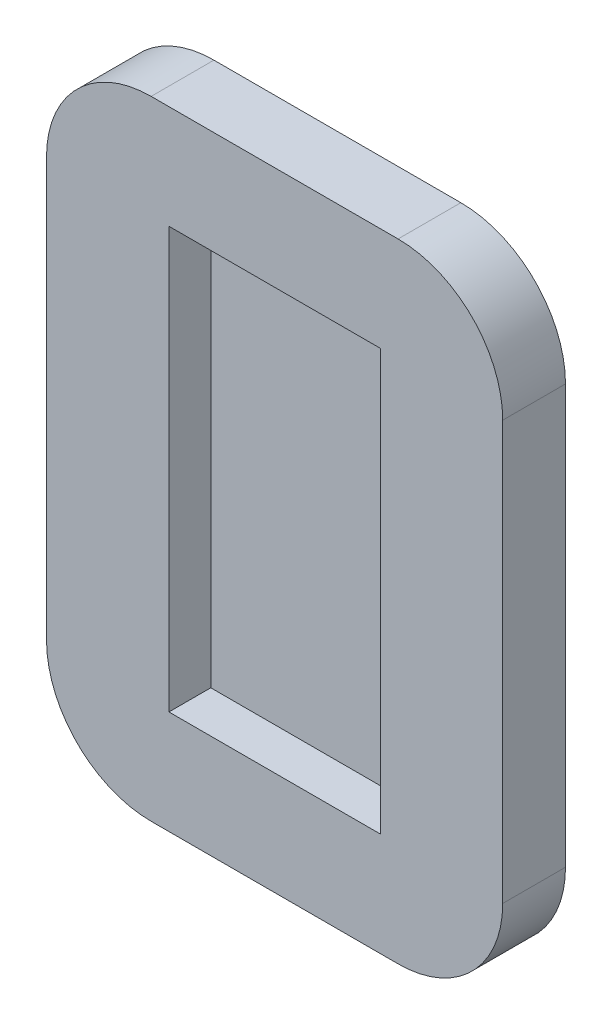
SolidWorks part; units mm, degrees
ref_plane "Alzado" through (0, 0, 0) normal (0, 0, 1) x (1, 0, 0)
ref_plane "Planta" through (0, 0, 0) normal (0, 1, 0) x (1, 0, 0)
ref_plane "Vista lateral" through (0, 0, 0) normal (1, 0, 0) x (0, 0, -1)
sketch "Croquis1" plane through (0, 0, 0) normal (1, 0, 0) x (0, 0, -1)
  line L1 (0, 0) -> (-21.8, 0)
  line L2 (0, 0) -> (0, -30)
  line L3 (0, -30) -> (-21.8, -30)
  line L4 (-21.8, 0) -> (-21.8, -30)
  dimension "D1" = 21.8
  dimension "D2" = 30
extrude "Saliente-Extruir1" add sketch "Croquis1" along normal blind 21.8 contours L2 L3 L4 L1
sketch "Croquis6" plane through (0, 0, 0) normal (-1, 0, 0) x (0, 0, 1)
  line L1 (10.9, -7) -> (10.9, 0) construction
  line L2 (10.9, -22) -> (10.9, -7) construction
  line L3 (0, 0) -> (21.8, 0) construction
  circle A0 centre (10.9, -22) radius 2
  circle A1 centre (10.9, -7) radius 2
  dimension "D1" = 15
  dimension "D3" = 4
  dimension "D4" = 4
  dimension "D2" = 7
extrude "Cortar-Extruir2" cut sketch "Croquis6" against normal up to surface (21.8 mm away) up to face at (21.8, -15, 10.9)
sketch "Croquis7" plane through (21.8, 0, 0) normal (1, 0, 0) x (0, 0, -1)
  line L2 (-10.9, -22) -> (-10.9, -7) construction
  circle A0 centre (-10.9, -22) radius 3.5
  circle A1 centre (-10.9, -7) radius 3.5
  circle A2 centre (-10.9, -7) radius 2 construction
  dimension "D1" = 7
  dimension "D2" = 7
  dimension "D3" = 15
sketch "Croquis11" plane through (0, -30, 0) normal (0, -1, 0) x (1, 0, 0)
  line L0 (13.4, 5.9) -> (13.4, 10.9) construction
  line L1 (0, 0) -> (0, 21.8) construction
  line L2 (0, 0) -> (0, 21.8) construction
  line L7 (16.9, 10.9) -> (21.8, 10.9) construction
  line L8 (13.4, 10.9) -> (8.9, 10.9) construction
  line L9 (8.9, 15.1) -> (5.5, 15.1)
  line L14 (8.9, 15.1) -> (8.9, 6.7)
  line L16 (8.9, 6.7) -> (5.5, 6.7)
  line L17 (5.5, 15.1) -> (5.5, 6.7)
  line L18 (21.8, 0) -> (21.8, 21.8) construction
  line L19 (5.5, 10.9) -> (0, 10.9) construction
  circle A1 centre (13.4, 10.9) radius 3.5
  dimension "D1" = 8.4
  dimension "D2" = 5.5
  dimension "D3" = 5
  dimension "D4" = 3.4
  dimension "D5" = 4.5
extrude "Cortar-Extruir4" cut sketch "Croquis11" against normal up to surface (30 mm away) and the other way blind 3.5 contours A1 | L14 L9 L17 L16 up to face at (10.9, 0, 10.9)
fillet "Redondeo1" radius 5 4 edges at (21.8, -30, 10.9) (0, -30, 10.9) (21.8, 0, 10.9) (0, 0, 10.9)
sketch "Croquis13" plane through (0, 0, 0) normal (-1, 0, 0) x (0, 0, 1)
  line L0 (10.9, -7) -> (10.9, -22) construction
  line L1 (10.9, -14.5) -> (2.8317, -14.5) construction
  circle A0 centre (10.9, -22) radius 2 construction
  circle A1 centre (10.9, -7) radius 2 construction
  circle A2 centre (10.9, -22) radius 2 construction
  circle A3 centre (10.9, -7) radius 2 construction
  circle A4 centre (10.9, -7) radius 3.5
  circle A5 centre (10.9, -22) radius 3.5
  dimension "D1" = 7
extrude "Cortar-Extruir6" cut sketch "Croquis13" against normal blind 3.5
sketch "Croquis16" plane through (0, 0, 21.8) normal (0, 0, 1) x (1, 0, 0)
  line L0 (10.9, 0) -> (10.9, -4.95) construction
  line L1 (16.8, 0) -> (5, 0) construction
  line L2 (10.9, -4.95) -> (5.85, -4.95) construction
  line L3 (10.9, -25.05) -> (10.9, -30) construction
  line L4 (5.85, -4.95) -> (15.95, -4.95)
  line L5 (5.85, -4.95) -> (5.85, -25.05)
  line L6 (5.85, -25.05) -> (15.95, -25.05)
  line L7 (15.95, -4.95) -> (15.95, -25.05)
  line L8 (0, -5) -> (0, -25) construction
  line L11 (15.95, -15) -> (21.8, -15) construction
  line L12 (21.8, -5) -> (21.8, -25) construction
  line L13 (16.8, -30) -> (5, -30) construction
  line L14 (5.85, -15) -> (0, -15) construction
  point P16 (0, 0)
  point P19 (0, 0)
  dimension "D1" = 5.85
  dimension "D2" = 10.1
  dimension "D3" = 20.1
  dimension "D4" = 4.95
  dimension "D5" = 5.85
extrude "Cortar-Extruir7" cut sketch "Croquis16" against normal blind 2
sketch "Croquis17" plane through (0, 0, 0) normal (0, 0, -1) x (-1, 0, 0)
  line L4 (-15.95, -25.05) -> (-15.95, -4.95) construction
  line L5 (-15.95, -4.95) -> (-5.85, -4.95) construction
  line L6 (-5.85, -4.95) -> (-5.85, -25.05) construction
  line L7 (-5.85, -25.05) -> (-15.95, -25.05) construction
  line L12 (-15.95, -25.05) -> (-15.95, -4.95)
  line L13 (-15.95, -4.95) -> (-5.85, -4.95)
  line L14 (-5.85, -4.95) -> (-5.85, -25.05)
  line L15 (-5.85, -25.05) -> (-15.95, -25.05)
extrude "Cortar-Extruir8" cut sketch "Croquis17" against normal blind 2.1
extrude "Cortar-Extruir9" cut sketch "Croquis7" against normal blind 3.5
sketch "Croquis18" plane through (0, 0, 0) normal (-1, 0, 0) x (0, 0, 1)
  line L0 (0, 0) -> (18.8, 0)
  line L2 (0, 0) -> (0, -30)
  line L3 (0, -30) -> (18.8, -30)
  line L5 (18.8, 0) -> (18.8, -30)
  dimension "D1" = 18.8
  dimension "D2" = 18.8
extrude "Cortar-Extruir10" cut sketch "Croquis18" against normal up to surface (21.8 mm away) up to face at (21.8, -14.875, 10.9)
